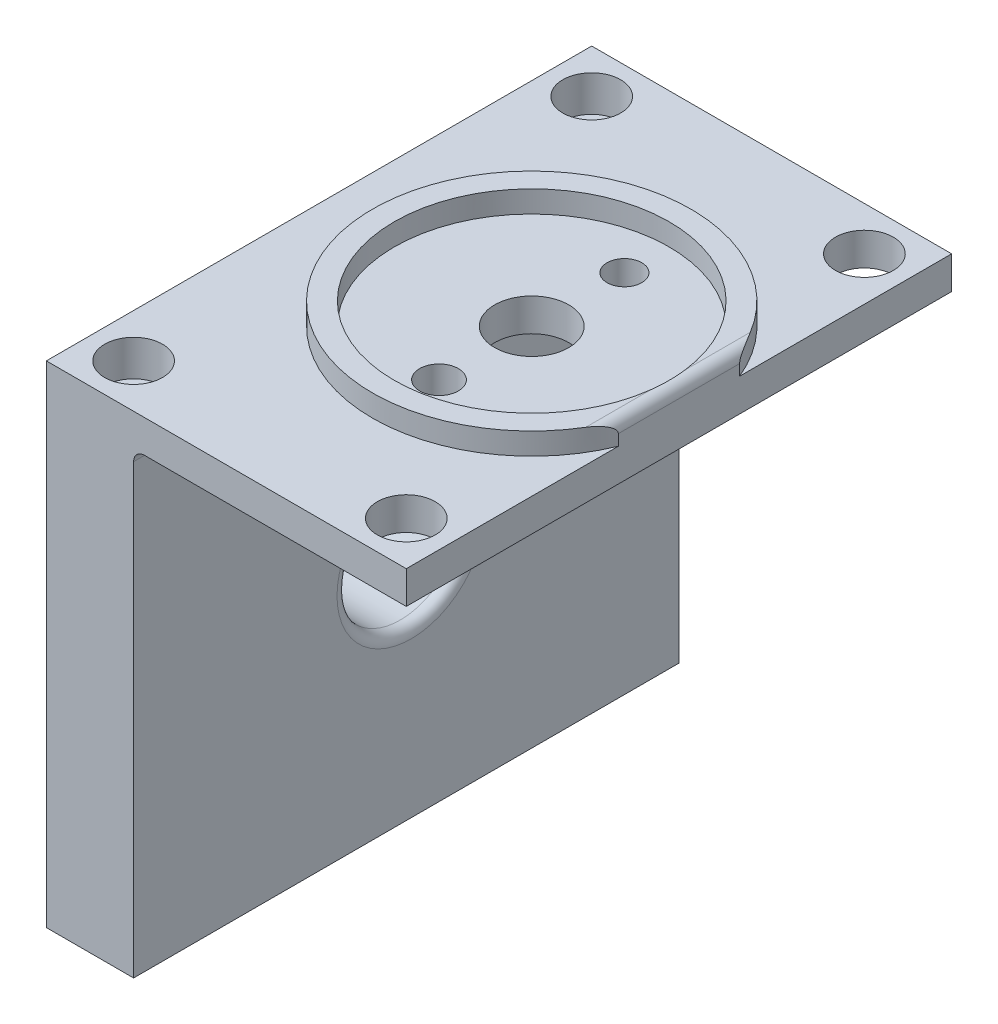
SolidWorks part; units mm, degrees
ref_plane "Front Plane" through (0, 0, 0) normal (0, 0, 1) x (1, 0, 0)
ref_plane "Top Plane" through (0, 0, 0) normal (0, 1, 0) x (1, 0, 0)
ref_plane "Right Plane" through (0, 0, 0) normal (1, 0, 0) x (0, 0, -1)
sketch "Sketch1" plane through (0, 0, 0) normal (0, 1, 0) x (1, 0, 0)
  line L1 (-10.223, 36.3848) -> (14.777, 36.3848)
  line L2 (-10.223, 36.3848) -> (-10.223, -13.6152)
  line L3 (-10.223, -13.6152) -> (14.777, -13.6152)
  line L4 (14.777, 36.3848) -> (14.777, -13.6152)
  circle A0 centre (1.277, 11.3848) radius 3.4
  dimension "D3" = 6.8
  dimension "D1" = 50
  dimension "D2" = 25
  dimension "D4" = 13.5
  dimension "D5" = 25
extrude "Boss-Extrude1" add sketch "Sketch1" along normal blind 3
sketch "Sketch2" plane through (-10.223, 0, 0) normal (-1, 0, 0) x (0, 0, 1)
  line L0 (18.15, 0) -> (-18.15, 0) construction
  line L1 (-36.3848, 3) -> (13.6152, 3)
  line L2 (-36.3848, 3) -> (-36.3848, 0)
  line L3 (-36.3848, 0) -> (13.6152, 0)
  line L4 (13.6152, 3) -> (13.6152, 0)
  line L5 (13.6152, 3) -> (13.6152, 0) construction
extrude "Boss-Extrude2" add sketch "Sketch2" along normal blind 8
sketch "Sketch3" plane through (0, 0, 0) normal (0, -1, 0) x (1, 0, 0)
  line L0 (-18.223, 13.6152) -> (14.777, 13.6152) construction
  line L1 (-18.223, -36.3848) -> (-10.223, -36.3848)
  line L2 (-18.223, -36.3848) -> (-18.223, 13.6152)
  line L3 (-18.223, 13.6152) -> (-10.223, 13.6152)
  line L4 (-10.223, -36.3848) -> (-10.223, 13.6152)
  dimension "D1" = 8
extrude "Boss-Extrude3" add sketch "Sketch3" along normal blind 42
sketch "Sketch4" plane through (0, 3, 0) normal (0, 1, 0) x (1, 0, 0)
  line L0 (-18.223, -13.6152) -> (-18.223, 36.3848) construction
  line L1 (14.777, 36.3848) -> (-18.223, 36.3848) construction
  line L2 (-18.223, -13.6152) -> (14.777, -13.6152) construction
  circle A0 centre (-14.223, 32.3848) radius 2.65
  circle A1 centre (-14.223, -9.6152) radius 2.65
  dimension "D2" = 5.3
  dimension "D4" = 5.3
  dimension "D5" = 4
  dimension "D6" = 4
  dimension "D1" = 4
  dimension "D3" = 4
extrude "Cut-Extrude1" cut sketch "Sketch4" against normal blind 3.3
ref_plane "Plane1" through (0, -19.5, 0) normal (0, 1, 0) x (1, 0, 0)
mirror "Mirror1" about plane through (0, -19.5, 0) normal (0, 1, 0) of "Cut-Extrude1"
sketch "Sketch5" plane through (-18.223, 0, 0) normal (-1, 0, 0) x (0, 0, 1)
  line L0 (18.15, 0) -> (-18.15, 0) construction
  line L1 (-6.9841, -24.1818) -> (-6.6547, -18.3888) construction
  line L2 (-6.6547, -18.3888) -> (-11.5069, -15.207) construction
  line L3 (-11.5069, -15.207) -> (-16.6885, -17.8182) construction
  line L4 (-16.6885, -17.8182) -> (-17.0179, -23.6112) construction
  line L5 (-17.0179, -23.6112) -> (-12.1657, -26.793) construction
  line L6 (-12.1657, -26.793) -> (-6.9841, -24.1818) construction
  circle A0 centre (-11.8363, -21) radius 5.025 construction
  circle A1 centre (-11.8363, -21) radius 5.8024
  dimension "D1" = 21
  dimension "D2" = 10.05
extrude "Cut-Extrude2" cut sketch "Sketch5" against normal blind 9
fillet "Fillet2" radius 1 1 edges at (-10.223, -21, -6.0339)
ref_plane "Plane2" through (-1.723, 0, 0) normal (-1, 0, 0) x (0, 0, 1)
mirror "Mirror2" about plane through (-1.723, 0, 0) normal (-1, 0, 0) of "Cut-Extrude1"
sketch "Sketch6" plane through (0, 3, 0) normal (0, 1, 0) x (1, 0, 0)
  line L0 (1.277, 14.7848) -> (1.277, 7.9848) construction
  line L1 (14.777, -13.6152) -> (14.777, 36.3848) construction
  line L2 (14.777, 16.9444) -> (14.777, 5.8251)
  circle A0 centre (1.277, 11.3848) radius 3.4 construction
  circle A1 centre (1.277, 11.3848) radius 3.1
  circle A2 centre (1.277, 11.3848) radius 12.6
  arc A3 (14.777, 16.9444) -> (14.777, 5.8251) centre (1.277, 11.3848) ccw
  line M9 (14.777, -13.6152) -> (14.777, 36.3848)
  dimension "D1" = 25.2
  dimension "D2" = 2
extrude "Boss-Extrude4" add sketch "Sketch6" along normal blind 2 contours A3 A2 M9 region at (14.3717, 3, -11.3848)
fillet "Fillet3" radius 1 1 edges at (-10.223, 0, -11.3848)
fillet "Fillet4" radius 1 1 edges at (14.777, 5, -11.3848)
sketch "Sketch8" plane through (0, 3, 0) normal (0, 1, 0) x (1, 0, 0)
  line L0 (4.677, 11.3848) -> (-2.123, 11.3848) construction
  circle A0 centre (1.277, 11.3848) radius 3.4 construction
  circle A1 centre (1.277, 19.8848) radius 1.5898
  circle A2 centre (1.277, 2.8848) radius 1.7774
  point P9 (1.277, 11.3848)
  dimension "D1" = 8.5
  dimension "D2" = 8.5
extrude "Cut-Extrude3" cut sketch "Sketch8" against normal blind 10
